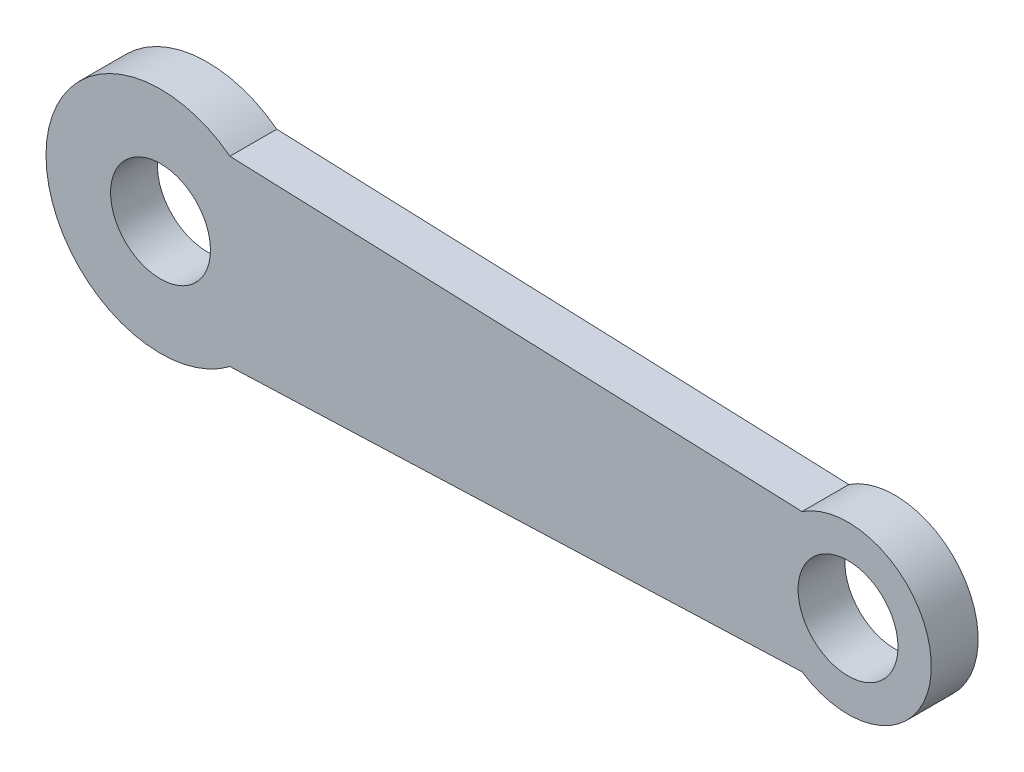
SolidWorks part; units mm, degrees
material "Plain Carbon Steel"
ref_plane "Front Plane" through (0, 0, 0) normal (0, 0, 1) x (1, 0, 0)
ref_plane "Top Plane" through (0, 0, 0) normal (0, 1, 0) x (1, 0, 0)
ref_plane "Right Plane" through (0, 0, 0) normal (1, 0, 0) x (0, 0, -1)
sketch "Sketch1" plane through (0, 0, 0) normal (0, 0, 1) x (1, 0, 0)
  circle A0 centre (0, 0) radius 11
  dimension "D1" = 22
extrude "Boss-Extrude1" add sketch "Sketch1" along normal mid plane 4.5
sketch "Sketch2" plane through (0, 0, 0) normal (0, 0, 1) x (1, 0, 0)
  circle A0 centre (66.0482, 0) radius 8
  dimension "D1" = 16
extrude "Boss-Extrude2" add sketch "Sketch2" along normal mid plane 4.5
sketch "Sketch3" plane through (0, 0, 0) normal (0, 0, 1) x (1, 0, 0)
  line L0 (0, -9) -> (66.0482, -6.5)
  line L1 (66.0482, -6.5) -> (66.0482, 6.5)
  line L2 (66.0482, 6.5) -> (0, 9)
  line L3 (0, 9) -> (0, -9)
extrude "Boss-Extrude3" add sketch "Sketch3" along normal mid plane 4.5
sketch "Sketch4" plane through (0, 0, 0) normal (0, 0, 1) x (1, 0, 0)
  circle A0 centre (0, 0) radius 4.8
  circle A1 centre (66.0482, 0) radius 4.8
  dimension "D1" = 9.6
  dimension "D2" = 9.6
extrude "Cut-Extrude1" cut sketch "Sketch4" against normal mid plane 9
